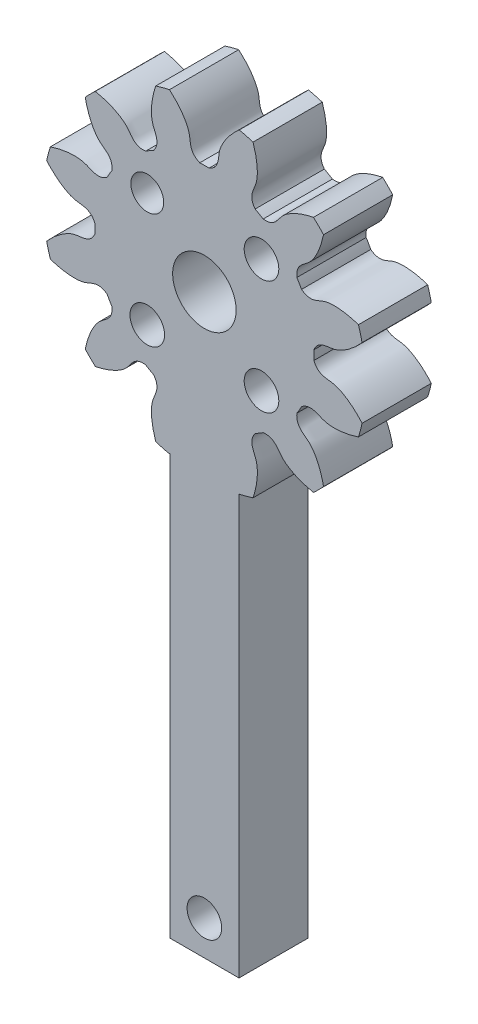
SolidWorks part; units mm, degrees
ref_plane "前视基准面" through (0, 0, 0) normal (0, 0, 1) x (1, 0, 0)
ref_plane "上视基准面" through (0, 0, 0) normal (0, 1, 0) x (1, 0, 0)
ref_plane "右视基准面" through (0, 0, 0) normal (1, 0, 0) x (0, 0, -1)
sketch "草图1" plane through (0, 0, 0) normal (0, 0, 1) x (1, 0, 0)
  circle A0 centre (0, 0) radius 14
extrude "凸台-拉伸1" add sketch "草图1" along normal blind 30
ref_axis "基准轴1" through (0, 0, 23.6995) along (0, 0, 1)
sketch "草图2" plane through (0, 0, 0) normal (0, 0, 1) x (1, 0, 0)
  line L0 (0, 0) -> (0, 14) construction
  circle A0 centre (0, 0) radius 14 construction
  arc A1 (0.4017, 9.4915) -> (-0.4017, 9.4915) centre (0, 0) ccw
  arc A2 (6.9952, 15.7899) -> (-6.9952, 15.7899) centre (0, 0) ccw
  spline S0 degree 3 poles (0.4017, 9.4915) (1.3616, 9.8986) (1.1487, 10.6896) (1.3523, 11.379) (1.3652, 11.4198) (1.3805, 11.4647) (1.3981, 11.5135) (1.4183, 11.5661) (1.4413, 11.6225) (1.4671, 11.6826) (1.4961, 11.7462) (1.5282, 11.8133) (1.5637, 11.8838) (1.6028, 11.9576) (1.6455, 12.0345) (1.6919, 12.1144) (1.7423, 12.1973) (1.7968, 12.2829) (1.8555, 12.3712) (1.9185, 12.462) (1.9859, 12.5552) (2.0579, 12.6506) (2.1346, 12.7481) (2.2161, 12.8475) (2.3025, 12.9487) (2.3939, 13.0516) (2.4904, 13.1559) (2.5921, 13.2615) (2.6991, 13.3682) (2.8114, 13.4759) (2.9292, 13.5844) (3.0525, 13.6935) (3.1814, 13.803) (3.316, 13.9128) (3.4563, 14.0226) (3.6023, 14.1323) (3.7542, 14.2418) (3.912, 14.3507) (4.0756, 14.4589) (4.2452, 14.5663) (4.4208, 14.6726) (4.6024, 14.7776) (4.79, 14.8811) (4.9836, 14.983) (5.1832, 15.083) (5.3889, 15.1809) (5.6006, 15.2765) (5.8183, 15.3697) (6.042, 15.4602) (6.2717, 15.5478) (6.5888, 15.6615) (6.8312, 15.7402) (6.9952, 15.7899) knots 0 0 0 0 0.218015 0.222044 0.226546 0.231522 0.236972 0.242897 0.249295 0.256167 0.263513 0.271332 0.279626 0.288394 0.297636 0.307351 0.317541 0.328204 0.339341 0.350953 0.363038 0.375597 0.38863 0.402137 0.416118 0.430573 0.445502 0.460904 0.476781 0.493132 0.509956 0.527255 0.545027 0.563273 0.581994 0.601188 0.620856 0.640998 0.661614 0.682704 0.704268 0.726305 0.748817 0.771803 0.795262 0.819196 0.843603 0.868484 0.89384 0.919669 0.945972 1 1 1 1
  spline S1 degree 3 poles (-0.4017, 9.4915) (-1.3616, 9.8986) (-1.1487, 10.6896) (-1.3523, 11.379) (-1.3652, 11.4198) (-1.3805, 11.4647) (-1.3981, 11.5135) (-1.4183, 11.5661) (-1.4413, 11.6225) (-1.4671, 11.6826) (-1.4961, 11.7462) (-1.5282, 11.8133) (-1.5637, 11.8838) (-1.6028, 11.9576) (-1.6455, 12.0345) (-1.6919, 12.1144) (-1.7423, 12.1973) (-1.7968, 12.2829) (-1.8555, 12.3712) (-1.9185, 12.462) (-1.9859, 12.5552) (-2.0579, 12.6506) (-2.1346, 12.7481) (-2.2161, 12.8475) (-2.3025, 12.9487) (-2.3939, 13.0516) (-2.4904, 13.1559) (-2.5921, 13.2615) (-2.6991, 13.3682) (-2.8114, 13.4759) (-2.9292, 13.5844) (-3.0525, 13.6935) (-3.1814, 13.803) (-3.316, 13.9128) (-3.4563, 14.0226) (-3.6023, 14.1323) (-3.7542, 14.2418) (-3.912, 14.3507) (-4.0756, 14.4589) (-4.2452, 14.5663) (-4.4208, 14.6726) (-4.6024, 14.7776) (-4.79, 14.8811) (-4.9836, 14.983) (-5.1832, 15.083) (-5.3889, 15.1809) (-5.6006, 15.2765) (-5.8183, 15.3697) (-6.042, 15.4602) (-6.2717, 15.5478) (-6.5888, 15.6615) (-6.8312, 15.7402) (-6.9952, 15.7899) knots 0 0 0 0 0.218015 0.222044 0.226546 0.231522 0.236972 0.242897 0.249295 0.256167 0.263513 0.271332 0.279626 0.288394 0.297636 0.307351 0.317541 0.328204 0.339341 0.350953 0.363038 0.375597 0.38863 0.402137 0.416118 0.430573 0.445502 0.460904 0.476781 0.493132 0.509956 0.527255 0.545027 0.563273 0.581994 0.601188 0.620856 0.640998 0.661614 0.682704 0.704268 0.726305 0.748817 0.771803 0.795262 0.819196 0.843603 0.868484 0.89384 0.919669 0.945972 1 1 1 1
extrude "切除-拉伸1" cut sketch "草图2" along normal through all
pattern_circular "阵列(圆周)1" count 12 every 30 about axis through (0, 0, 23.6995) along (0, 0, 1) of "切除-拉伸1"
sketch "草图3" plane through (0, 0, 0) normal (0, 0, 1) x (1, 0, 0)
  circle A0 centre (0, 0) radius 12 construction
  dimension "Dn" = 24
sketch "草图4" plane through (0, 0, 30) normal (0, 0, 1) x (1, 0, 0)
  line L0 (-4.75, 8.2272) -> (4.75, 8.2272) construction
  line L1 (4.95, -4.95) -> (-4.95, -4.95) construction
  line L2 (4.95, -4.95) -> (4.95, 4.95) construction
  line L3 (4.95, 4.95) -> (-4.95, 4.95) construction
  line L4 (-4.95, -4.95) -> (-4.95, 4.95) construction
  line L5 (4.95, -4.95) -> (-4.95, 4.95) construction
  line L6 (4.95, 4.95) -> (-4.95, -4.95) construction
  circle A0 centre (4.95, 4.95) radius 1.5
  circle A1 centre (4.95, -4.95) radius 1.5
  circle A2 centre (-4.95, -4.95) radius 1.5
  circle A3 centre (-4.95, 4.95) radius 1.4237
  arc A4 (-4.3979, 8.4207) -> (-5.0936, 8.019) centre (0, 0) ccw construction
  arc A5 (5.0936, 8.019) -> (4.3979, 8.4207) centre (0, 0) ccw construction
  point P0 (0, 0)
  dimension "D3" = 3
  dimension "D1" = 9.9
  dimension "D2" = 9.9
extrude "切除-拉伸2" cut sketch "草图4" against normal blind 10
sketch "草图5" plane through (0, 0, 0) normal (0, 0, -1) x (-1, 0, 0)
  arc A24 (5.0936, 8.019) -> (4.3979, 8.4207) centre (0, 0) ccw
  arc A25 (4.2145, 13.3506) -> (3.0255, 13.6692) centre (0, 0) ccw
  arc A26 (0.4017, 9.4915) -> (-0.4017, 9.4915) centre (0, 0) ccw
  arc A27 (-3.0255, 13.6692) -> (-4.2145, 13.3506) centre (0, 0) ccw
  arc A28 (-4.3979, 8.4207) -> (-5.0936, 8.019) centre (0, 0) ccw
  arc A29 (-9.4547, 10.3251) -> (-10.3251, 9.4547) centre (0, 0) ccw
  arc A30 (-8.019, 5.0936) -> (-8.4207, 4.3979) centre (0, 0) ccw
  arc A31 (-13.3506, 4.2145) -> (-13.6692, 3.0255) centre (0, 0) ccw
  arc A32 (-9.4915, 0.4017) -> (-9.4915, -0.4017) centre (0, 0) ccw
  arc A33 (-13.6692, -3.0255) -> (-13.3506, -4.2145) centre (0, 0) ccw
  arc A34 (-8.4207, -4.3979) -> (-8.019, -5.0936) centre (0, 0) ccw
  arc A35 (-10.3251, -9.4547) -> (-9.4547, -10.3251) centre (0, 0) ccw
  arc A36 (-5.0936, -8.019) -> (-4.3979, -8.4207) centre (0, 0) ccw
  arc A37 (-4.2145, -13.3506) -> (-3.0255, -13.6692) centre (0, 0) ccw
  arc A38 (-0.4017, -9.4915) -> (0.4017, -9.4915) centre (0, 0) ccw
  arc A39 (3.0255, -13.6692) -> (4.2145, -13.3506) centre (0, 0) ccw
  arc A40 (4.3979, -8.4207) -> (5.0936, -8.019) centre (0, 0) ccw
  arc A41 (9.4547, -10.3251) -> (10.3251, -9.4547) centre (0, 0) ccw
  arc A42 (8.019, -5.0936) -> (8.4207, -4.3979) centre (0, 0) ccw
  arc A43 (13.3506, -4.2145) -> (13.6692, -3.0255) centre (0, 0) ccw
  arc A44 (9.4915, -0.4017) -> (9.4915, 0.4017) centre (0, 0) ccw
  arc A45 (13.6692, 3.0255) -> (13.3506, 4.2145) centre (0, 0) ccw
  arc A46 (8.4207, 4.3979) -> (8.019, 5.0936) centre (0, 0) ccw
  arc A47 (10.3251, 9.4547) -> (9.4547, 10.3251) centre (0, 0) ccw
  arc A48 (5.0936, 8.019) -> (4.3979, 8.4207) centre (0, 0) ccw
  arc A49 (4.2145, 13.3506) -> (3.0255, 13.6692) centre (0, 0) ccw
  arc A50 (0.4017, 9.4915) -> (-0.4017, 9.4915) centre (0, 0) ccw
  arc A51 (-3.0255, 13.6692) -> (-4.2145, 13.3506) centre (0, 0) ccw
  arc A52 (-4.3979, 8.4207) -> (-5.0936, 8.019) centre (0, 0) ccw
  arc A53 (-9.4547, 10.3251) -> (-10.3251, 9.4547) centre (0, 0) ccw
  arc A54 (-8.019, 5.0936) -> (-8.4207, 4.3979) centre (0, 0) ccw
  arc A55 (-13.3506, 4.2145) -> (-13.6692, 3.0255) centre (0, 0) ccw
  arc A56 (-9.4915, 0.4017) -> (-9.4915, -0.4017) centre (0, 0) ccw
  arc A57 (-13.6692, -3.0255) -> (-13.3506, -4.2145) centre (0, 0) ccw
  arc A58 (-8.4207, -4.3979) -> (-8.019, -5.0936) centre (0, 0) ccw
  arc A59 (-10.3251, -9.4547) -> (-9.4547, -10.3251) centre (0, 0) ccw
  arc A60 (-5.0936, -8.019) -> (-4.3979, -8.4207) centre (0, 0) ccw
  arc A61 (-4.2145, -13.3506) -> (-3.0255, -13.6692) centre (0, 0) ccw
  arc A62 (-0.4017, -9.4915) -> (0.4017, -9.4915) centre (0, 0) ccw
  arc A63 (3.0255, -13.6692) -> (4.2145, -13.3506) centre (0, 0) ccw
  arc A64 (4.3979, -8.4207) -> (5.0936, -8.019) centre (0, 0) ccw
  arc A65 (9.4547, -10.3251) -> (10.3251, -9.4547) centre (0, 0) ccw
  arc A66 (8.019, -5.0936) -> (8.4207, -4.3979) centre (0, 0) ccw
  arc A67 (13.3506, -4.2145) -> (13.6692, -3.0255) centre (0, 0) ccw
  arc A68 (9.4915, -0.4017) -> (9.4915, 0.4017) centre (0, 0) ccw
  arc A69 (13.6692, 3.0255) -> (13.3506, 4.2145) centre (0, 0) ccw
  arc A70 (8.4207, 4.3979) -> (8.019, 5.0936) centre (0, 0) ccw
  arc A71 (10.3251, 9.4547) -> (9.4547, 10.3251) centre (0, 0) ccw
  spline S24 degree 3 poles (-2368.8794, 1837.9661) (113.0421, -150.6443) (38.3111, 18.3423) (8.7386, 10.1508) (8.4722, 10.0654) (8.2264, 9.9757) (8.0011, 9.883) (7.7961, 9.789) (7.6111, 9.695) (7.4457, 9.6025) (7.2995, 9.5129) (7.172, 9.4276) (7.0778, 9.359) (6.9977, 9.2968) (6.9309, 9.2418) (6.8721, 9.1892) (0.5786, 3.2069) (39.4786, -48.9386) (-2052.1534, 2191.1398) knots -9.086932 -9.086932 -9.086932 -9.086932 0.523219 0.554498 0.583882 0.61137 0.636962 0.660659 0.682459 0.702364 0.720374 0.736487 0.750705 0.757103 0.768478 0.777956 0.781985 3.505334 3.505334 3.505334 3.505334 only from (9.4547, 10.3251) to (5.0936, 8.019)
  spline S25 degree 3 poles (2923.6721, -681.6501) (-62.1215, 9.7202) (2.4879, 2.1045) (4.522, 10.546) (4.5381, 10.6233) (4.556, 10.7301) (4.5718, 10.8554) (4.5842, 10.9992) (4.5917, 11.1614) (4.5929, 11.3419) (4.5862, 11.5403) (4.5702, 11.7563) (4.5437, 11.9893) (4.505, 12.239) (4.453, 12.5046) (4.3862, 12.7855) (-4.0276, 42.7945) (-187.8553, 19.7333) (2778.1998, -1127.4538) knots -2.505338 -2.505338 -2.505338 -2.505338 0.218015 0.222044 0.231522 0.242897 0.256167 0.271332 0.288394 0.307351 0.328204 0.350953 0.375597 0.402137 0.430573 0.460904 0.493132 10.252695 10.252695 10.252695 10.252695 only from (4.3979, 8.4207) to (4.2145, 13.3506)
  spline S26 degree 3 poles (-2970.4928, 407.2856) (173.2195, -73.9407) (24.0073, 35.0405) (2.4924, 13.1601) (2.3045, 12.953) (2.1365, 12.7524) (1.9877, 12.5595) (1.8571, 12.3755) (1.7439, 12.2016) (1.6469, 12.0389) (1.5651, 11.8882) (1.4973, 11.7506) (1.4501, 11.6441) (1.4118, 11.5501) (1.3815, 11.4691) (1.3568, 11.3941) (-1.1024, 3.0665) (58.6587, -22.6428) (-2872.7869, 871.506) knots -9.086932 -9.086932 -9.086932 -9.086932 0.523219 0.554498 0.583882 0.61137 0.636962 0.660659 0.682459 0.702364 0.720374 0.736487 0.750705 0.757103 0.768478 0.777956 0.781985 3.505334 3.505334 3.505334 3.505334 only from (3.0255, 13.6692) to (0.4017, 9.4915)
  spline S27 degree 3 poles (2872.7993, 871.5098) (-58.6589, -22.6429) (1.1024, 3.0665) (-1.3568, 11.3941) (-1.3815, 11.4691) (-1.4194, 11.5705) (-1.4684, 11.687) (-1.5295, 11.8177) (-1.6042, 11.962) (-1.6934, 12.1188) (-1.7984, 12.2873) (-1.9202, 12.4663) (-2.0597, 12.6549) (-2.218, 12.8518) (-2.3959, 13.0558) (-2.5942, 13.2657) (-24.8852, 35.0474) (-172.5541, -76.8381) (2969.7185, 412.6963) knots -2.505338 -2.505338 -2.505338 -2.505338 0.218015 0.222044 0.231522 0.242897 0.256167 0.271332 0.288394 0.307351 0.328204 0.350953 0.375597 0.402137 0.430573 0.460904 0.493132 10.252695 10.252695 10.252695 10.252695 only from (-0.4017, 9.4915) to (-3.0255, 13.6692)
  spline S28 degree 3 poles (-2776.1651, -1132.5267) (186.9828, 22.5752) (3.2707, 42.3496) (-4.4215, 12.6432) (-4.4808, 12.3699) (-4.5259, 12.1121) (-4.5584, 11.8707) (-4.5794, 11.6461) (-4.5906, 11.4389) (-4.5932, 11.2494) (-4.5887, 11.078) (-4.5786, 10.925) (-4.5662, 10.8091) (-4.5524, 10.7085) (-4.5381, 10.6233) (-4.522, 10.546) (-2.4879, 2.1045) (62.1214, 9.7201) (-2923.6594, -681.6471) knots -9.086932 -9.086932 -9.086932 -9.086932 0.523219 0.554498 0.583882 0.61137 0.636962 0.660659 0.682459 0.702364 0.720374 0.736487 0.750705 0.757103 0.768478 0.777956 0.781985 3.505334 3.505334 3.505334 3.505334 only from (-4.2145, 13.3506) to (-4.3979, 8.4207)
  spline S29 degree 3 poles (2052.1623, 2191.1493) (-39.4787, -48.9387) (-0.5786, 3.2069) (-6.8721, 9.1892) (-6.9309, 9.2418) (-7.0145, 9.3106) (-7.1151, 9.387) (-7.2335, 9.4697) (-7.3702, 9.5573) (-7.5259, 9.6485) (-7.7011, 9.7419) (-7.8961, 9.8361) (-8.1112, 9.9296) (-8.3468, 10.021) (-8.6028, 10.1087) (-8.8795, 10.1914) (-39.0749, 17.9093) (-111.0172, -152.8208) (2365.5035, 1842.2647) knots -2.505338 -2.505338 -2.505338 -2.505338 0.218015 0.222044 0.231522 0.242897 0.256167 0.271332 0.288394 0.307351 0.328204 0.350953 0.375597 0.402137 0.430573 0.460904 0.493132 10.252695 10.252695 10.252695 10.252695 only from (-5.0936, 8.019) to (-9.4547, 10.3251)
  spline S30 degree 3 poles (-1837.9661, -2368.8794) (150.6443, 113.0421) (-18.3423, 38.3111) (-10.1508, 8.7386) (-10.0654, 8.4722) (-9.9757, 8.2264) (-9.883, 8.0011) (-9.789, 7.7961) (-9.695, 7.6111) (-9.6025, 7.4457) (-9.5129, 7.2995) (-9.4276, 7.172) (-9.359, 7.0778) (-9.2968, 6.9977) (-9.2418, 6.9309) (-9.1892, 6.8721) (-3.2069, 0.5786) (48.9386, 39.4786) (-2191.1398, -2052.1534) knots -9.086932 -9.086932 -9.086932 -9.086932 0.523219 0.554498 0.583882 0.61137 0.636962 0.660659 0.682459 0.702364 0.720374 0.736487 0.750705 0.757103 0.768478 0.777956 0.781985 3.505334 3.505334 3.505334 3.505334 only from (-10.3251, 9.4547) to (-8.019, 5.0936)
  spline S31 degree 3 poles (681.6501, 2923.6721) (-9.7202, -62.1215) (-2.1045, 2.4879) (-10.546, 4.522) (-10.6233, 4.5381) (-10.7301, 4.556) (-10.8554, 4.5718) (-10.9992, 4.5842) (-11.1614, 4.5917) (-11.3419, 4.5929) (-11.5403, 4.5862) (-11.7563, 4.5702) (-11.9893, 4.5437) (-12.239, 4.505) (-12.5046, 4.453) (-12.7855, 4.3862) (-42.7945, -4.0276) (-19.7333, -187.8553) (1127.4538, 2778.1998) knots -2.505338 -2.505338 -2.505338 -2.505338 0.218015 0.222044 0.231522 0.242897 0.256167 0.271332 0.288394 0.307351 0.328204 0.350953 0.375597 0.402137 0.430573 0.460904 0.493132 10.252695 10.252695 10.252695 10.252695 only from (-8.4207, 4.3979) to (-13.3506, 4.2145)
  spline S32 degree 3 poles (-407.2856, -2970.4928) (73.9407, 173.2195) (-35.0405, 24.0073) (-13.1601, 2.4924) (-12.953, 2.3045) (-12.7524, 2.1365) (-12.5595, 1.9877) (-12.3755, 1.8571) (-12.2016, 1.7439) (-12.0389, 1.6469) (-11.8882, 1.5651) (-11.7506, 1.4973) (-11.6441, 1.4501) (-11.5501, 1.4118) (-11.4691, 1.3815) (-11.3941, 1.3568) (-3.0665, -1.1024) (22.6428, 58.6587) (-871.506, -2872.7869) knots -9.086932 -9.086932 -9.086932 -9.086932 0.523219 0.554498 0.583882 0.61137 0.636962 0.660659 0.682459 0.702364 0.720374 0.736487 0.750705 0.757103 0.768478 0.777956 0.781985 3.505334 3.505334 3.505334 3.505334 only from (-13.6692, 3.0255) to (-9.4915, 0.4017)
  spline S33 degree 3 poles (-871.5098, 2872.7993) (22.6429, -58.6589) (-3.0665, 1.1024) (-11.3941, -1.3568) (-11.4691, -1.3815) (-11.5705, -1.4194) (-11.687, -1.4684) (-11.8177, -1.5295) (-11.962, -1.6042) (-12.1188, -1.6934) (-12.2873, -1.7984) (-12.4663, -1.9202) (-12.6549, -2.0597) (-12.8518, -2.218) (-13.0558, -2.3959) (-13.2657, -2.5942) (-35.0474, -24.8852) (76.8381, -172.5541) (-412.6963, 2969.7185) knots -2.505338 -2.505338 -2.505338 -2.505338 0.218015 0.222044 0.231522 0.242897 0.256167 0.271332 0.288394 0.307351 0.328204 0.350953 0.375597 0.402137 0.430573 0.460904 0.493132 10.252695 10.252695 10.252695 10.252695 only from (-9.4915, -0.4017) to (-13.6692, -3.0255)
  spline S34 degree 3 poles (1132.5267, -2776.1651) (-22.5752, 186.9828) (-42.3496, 3.2707) (-12.6432, -4.4215) (-12.3699, -4.4808) (-12.1121, -4.5259) (-11.8707, -4.5584) (-11.6461, -4.5794) (-11.4389, -4.5906) (-11.2494, -4.5932) (-11.078, -4.5887) (-10.925, -4.5786) (-10.8091, -4.5662) (-10.7085, -4.5524) (-10.6233, -4.5381) (-10.546, -4.522) (-2.1045, -2.4879) (-9.7201, 62.1214) (681.6471, -2923.6594) knots -9.086932 -9.086932 -9.086932 -9.086932 0.523219 0.554498 0.583882 0.61137 0.636962 0.660659 0.682459 0.702364 0.720374 0.736487 0.750705 0.757103 0.768478 0.777956 0.781985 3.505334 3.505334 3.505334 3.505334 only from (-13.3506, -4.2145) to (-8.4207, -4.3979)
  spline S35 degree 3 poles (-2191.1493, 2052.1623) (48.9387, -39.4787) (-3.2069, -0.5786) (-9.1892, -6.8721) (-9.2418, -6.9309) (-9.3106, -7.0145) (-9.387, -7.1151) (-9.4697, -7.2335) (-9.5573, -7.3702) (-9.6485, -7.5259) (-9.7419, -7.7011) (-9.8361, -7.8961) (-9.9296, -8.1112) (-10.021, -8.3468) (-10.1087, -8.6028) (-10.1914, -8.8795) (-17.9093, -39.0749) (152.8208, -111.0172) (-1842.2647, 2365.5035) knots -2.505338 -2.505338 -2.505338 -2.505338 0.218015 0.222044 0.231522 0.242897 0.256167 0.271332 0.288394 0.307351 0.328204 0.350953 0.375597 0.402137 0.430573 0.460904 0.493132 10.252695 10.252695 10.252695 10.252695 only from (-8.019, -5.0936) to (-10.3251, -9.4547)
  spline S36 degree 3 poles (2368.8794, -1837.9661) (-113.0421, 150.6443) (-38.3111, -18.3423) (-8.7386, -10.1508) (-8.4722, -10.0654) (-8.2264, -9.9757) (-8.0011, -9.883) (-7.7961, -9.789) (-7.6111, -9.695) (-7.4457, -9.6025) (-7.2995, -9.5129) (-7.172, -9.4276) (-7.0778, -9.359) (-6.9977, -9.2968) (-6.9309, -9.2418) (-6.8721, -9.1892) (-0.5786, -3.2069) (-39.4786, 48.9386) (2052.1534, -2191.1398) knots -9.086932 -9.086932 -9.086932 -9.086932 0.523219 0.554498 0.583882 0.61137 0.636962 0.660659 0.682459 0.702364 0.720374 0.736487 0.750705 0.757103 0.768478 0.777956 0.781985 3.505334 3.505334 3.505334 3.505334 only from (-9.4547, -10.3251) to (-5.0936, -8.019)
  spline S37 degree 3 poles (-2923.6721, 681.6501) (62.1215, -9.7202) (-2.4879, -2.1045) (-4.522, -10.546) (-4.5381, -10.6233) (-4.556, -10.7301) (-4.5718, -10.8554) (-4.5842, -10.9992) (-4.5917, -11.1614) (-4.5929, -11.3419) (-4.5862, -11.5403) (-4.5702, -11.7563) (-4.5437, -11.9893) (-4.505, -12.239) (-4.453, -12.5046) (-4.3862, -12.7855) (4.0276, -42.7945) (187.8553, -19.7333) (-2778.1998, 1127.4538) knots -2.505338 -2.505338 -2.505338 -2.505338 0.218015 0.222044 0.231522 0.242897 0.256167 0.271332 0.288394 0.307351 0.328204 0.350953 0.375597 0.402137 0.430573 0.460904 0.493132 10.252695 10.252695 10.252695 10.252695 only from (-4.3979, -8.4207) to (-4.2145, -13.3506)
  spline S38 degree 3 poles (2970.4928, -407.2856) (-173.2195, 73.9407) (-24.0073, -35.0405) (-2.4924, -13.1601) (-2.3045, -12.953) (-2.1365, -12.7524) (-1.9877, -12.5595) (-1.8571, -12.3755) (-1.7439, -12.2016) (-1.6469, -12.0389) (-1.5651, -11.8882) (-1.4973, -11.7506) (-1.4501, -11.6441) (-1.4118, -11.5501) (-1.3815, -11.4691) (-1.3568, -11.3941) (1.1024, -3.0665) (-58.6587, 22.6428) (2872.7869, -871.506) knots -9.086932 -9.086932 -9.086932 -9.086932 0.523219 0.554498 0.583882 0.61137 0.636962 0.660659 0.682459 0.702364 0.720374 0.736487 0.750705 0.757103 0.768478 0.777956 0.781985 3.505334 3.505334 3.505334 3.505334 only from (-3.0255, -13.6692) to (-0.4017, -9.4915)
  spline S39 degree 3 poles (-2872.7993, -871.5098) (58.6589, 22.6429) (-1.1024, -3.0665) (1.3568, -11.3941) (1.3815, -11.4691) (1.4194, -11.5705) (1.4684, -11.687) (1.5295, -11.8177) (1.6042, -11.962) (1.6934, -12.1188) (1.7984, -12.2873) (1.9202, -12.4663) (2.0597, -12.6549) (2.218, -12.8518) (2.3959, -13.0558) (2.5942, -13.2657) (24.8852, -35.0474) (172.5541, 76.8381) (-2969.7185, -412.6963) knots -2.505338 -2.505338 -2.505338 -2.505338 0.218015 0.222044 0.231522 0.242897 0.256167 0.271332 0.288394 0.307351 0.328204 0.350953 0.375597 0.402137 0.430573 0.460904 0.493132 10.252695 10.252695 10.252695 10.252695 only from (0.4017, -9.4915) to (3.0255, -13.6692)
  spline S40 degree 3 poles (2776.1651, 1132.5267) (-186.9828, -22.5752) (-3.2707, -42.3496) (4.4215, -12.6432) (4.4808, -12.3699) (4.5259, -12.1121) (4.5584, -11.8707) (4.5794, -11.6461) (4.5906, -11.4389) (4.5932, -11.2494) (4.5887, -11.078) (4.5786, -10.925) (4.5662, -10.8091) (4.5524, -10.7085) (4.5381, -10.6233) (4.522, -10.546) (2.4879, -2.1045) (-62.1214, -9.7201) (2923.6594, 681.6471) knots -9.086932 -9.086932 -9.086932 -9.086932 0.523219 0.554498 0.583882 0.61137 0.636962 0.660659 0.682459 0.702364 0.720374 0.736487 0.750705 0.757103 0.768478 0.777956 0.781985 3.505334 3.505334 3.505334 3.505334 only from (4.2145, -13.3506) to (4.3979, -8.4207)
  spline S41 degree 3 poles (-2052.1623, -2191.1493) (39.4787, 48.9387) (0.5786, -3.2069) (6.8721, -9.1892) (6.9309, -9.2418) (7.0145, -9.3106) (7.1151, -9.387) (7.2335, -9.4697) (7.3702, -9.5573) (7.5259, -9.6485) (7.7011, -9.7419) (7.8961, -9.8361) (8.1112, -9.9296) (8.3468, -10.021) (8.6028, -10.1087) (8.8795, -10.1914) (39.0749, -17.9093) (111.0172, 152.8208) (-2365.5035, -1842.2647) knots -2.505338 -2.505338 -2.505338 -2.505338 0.218015 0.222044 0.231522 0.242897 0.256167 0.271332 0.288394 0.307351 0.328204 0.350953 0.375597 0.402137 0.430573 0.460904 0.493132 10.252695 10.252695 10.252695 10.252695 only from (5.0936, -8.019) to (9.4547, -10.3251)
  spline S42 degree 3 poles (1837.9661, 2368.8794) (-150.6443, -113.0421) (18.3423, -38.3111) (10.1508, -8.7386) (10.0654, -8.4722) (9.9757, -8.2264) (9.883, -8.0011) (9.789, -7.7961) (9.695, -7.6111) (9.6025, -7.4457) (9.5129, -7.2995) (9.4276, -7.172) (9.359, -7.0778) (9.2968, -6.9977) (9.2418, -6.9309) (9.1892, -6.8721) (3.2069, -0.5786) (-48.9386, -39.4786) (2191.1398, 2052.1534) knots -9.086932 -9.086932 -9.086932 -9.086932 0.523219 0.554498 0.583882 0.61137 0.636962 0.660659 0.682459 0.702364 0.720374 0.736487 0.750705 0.757103 0.768478 0.777956 0.781985 3.505334 3.505334 3.505334 3.505334 only from (10.3251, -9.4547) to (8.019, -5.0936)
  spline S43 degree 3 poles (-681.6501, -2923.6721) (9.7202, 62.1215) (2.1045, -2.4879) (10.546, -4.522) (10.6233, -4.5381) (10.7301, -4.556) (10.8554, -4.5718) (10.9992, -4.5842) (11.1614, -4.5917) (11.3419, -4.5929) (11.5403, -4.5862) (11.7563, -4.5702) (11.9893, -4.5437) (12.239, -4.505) (12.5046, -4.453) (12.7855, -4.3862) (42.7945, 4.0276) (19.7333, 187.8553) (-1127.4538, -2778.1998) knots -2.505338 -2.505338 -2.505338 -2.505338 0.218015 0.222044 0.231522 0.242897 0.256167 0.271332 0.288394 0.307351 0.328204 0.350953 0.375597 0.402137 0.430573 0.460904 0.493132 10.252695 10.252695 10.252695 10.252695 only from (8.4207, -4.3979) to (13.3506, -4.2145)
  spline S44 degree 3 poles (407.2856, 2970.4928) (-73.9407, -173.2195) (35.0405, -24.0073) (13.1601, -2.4924) (12.953, -2.3045) (12.7524, -2.1365) (12.5595, -1.9877) (12.3755, -1.8571) (12.2016, -1.7439) (12.0389, -1.6469) (11.8882, -1.5651) (11.7506, -1.4973) (11.6441, -1.4501) (11.5501, -1.4118) (11.4691, -1.3815) (11.3941, -1.3568) (3.0665, 1.1024) (-22.6428, -58.6587) (871.506, 2872.7869) knots -9.086932 -9.086932 -9.086932 -9.086932 0.523219 0.554498 0.583882 0.61137 0.636962 0.660659 0.682459 0.702364 0.720374 0.736487 0.750705 0.757103 0.768478 0.777956 0.781985 3.505334 3.505334 3.505334 3.505334 only from (13.6692, -3.0255) to (9.4915, -0.4017)
  spline S45 degree 3 poles (871.5098, -2872.7993) (-22.6429, 58.6589) (3.0665, -1.1024) (11.3941, 1.3568) (11.4691, 1.3815) (11.5705, 1.4194) (11.687, 1.4684) (11.8177, 1.5295) (11.962, 1.6042) (12.1188, 1.6934) (12.2873, 1.7984) (12.4663, 1.9202) (12.6549, 2.0597) (12.8518, 2.218) (13.0558, 2.3959) (13.2657, 2.5942) (35.0474, 24.8852) (-76.8381, 172.5541) (412.6963, -2969.7185) knots -2.505338 -2.505338 -2.505338 -2.505338 0.218015 0.222044 0.231522 0.242897 0.256167 0.271332 0.288394 0.307351 0.328204 0.350953 0.375597 0.402137 0.430573 0.460904 0.493132 10.252695 10.252695 10.252695 10.252695 only from (9.4915, 0.4017) to (13.6692, 3.0255)
  spline S46 degree 3 poles (-1132.5267, 2776.1651) (22.5752, -186.9828) (42.3496, -3.2707) (12.6432, 4.4215) (12.3699, 4.4808) (12.1121, 4.5259) (11.8707, 4.5584) (11.6461, 4.5794) (11.4389, 4.5906) (11.2494, 4.5932) (11.078, 4.5887) (10.925, 4.5786) (10.8091, 4.5662) (10.7085, 4.5524) (10.6233, 4.5381) (10.546, 4.522) (2.1045, 2.4879) (9.7201, -62.1214) (-681.6471, 2923.6594) knots -9.086932 -9.086932 -9.086932 -9.086932 0.523219 0.554498 0.583882 0.61137 0.636962 0.660659 0.682459 0.702364 0.720374 0.736487 0.750705 0.757103 0.768478 0.777956 0.781985 3.505334 3.505334 3.505334 3.505334 only from (13.3506, 4.2145) to (8.4207, 4.3979)
  spline S47 degree 3 poles (2191.1493, -2052.1623) (-48.9387, 39.4787) (3.2069, 0.5786) (9.1892, 6.8721) (9.2418, 6.9309) (9.3106, 7.0145) (9.387, 7.1151) (9.4697, 7.2335) (9.5573, 7.3702) (9.6485, 7.5259) (9.7419, 7.7011) (9.8361, 7.8961) (9.9296, 8.1112) (10.021, 8.3468) (10.1087, 8.6028) (10.1914, 8.8795) (17.9093, 39.0749) (-152.8208, 111.0172) (1842.2647, -2365.5035) knots -2.505338 -2.505338 -2.505338 -2.505338 0.218015 0.222044 0.231522 0.242897 0.256167 0.271332 0.288394 0.307351 0.328204 0.350953 0.375597 0.402137 0.430573 0.460904 0.493132 10.252695 10.252695 10.252695 10.252695 only from (8.019, 5.0936) to (10.3251, 9.4547)
  spline S48 degree 3 poles (9.4547, 10.3251) (9.309, 10.2963) (9.0672, 10.2418) (8.7386, 10.1508) (8.4722, 10.0654) (8.2264, 9.9757) (8.0011, 9.883) (7.7961, 9.789) (7.6111, 9.695) (7.4457, 9.6025) (7.2995, 9.5129) (7.172, 9.4276) (7.0778, 9.359) (6.9977, 9.2968) (6.9309, 9.2418) (6.8721, 9.1892) (6.3397, 8.6831) (6.1285, 7.8917) (5.0936, 8.019) knots 0.476404 0.476404 0.476404 0.476404 0.523219 0.554498 0.583882 0.61137 0.636962 0.660659 0.682459 0.702364 0.720374 0.736487 0.750705 0.757103 0.768478 0.777956 0.781985 1 1 1 1
  spline S49 degree 3 poles (4.3979, 8.4207) (3.7701, 9.2532) (4.35, 9.8319) (4.522, 10.546) (4.5381, 10.6233) (4.556, 10.7301) (4.5718, 10.8554) (4.5842, 10.9992) (4.5917, 11.1614) (4.5929, 11.3419) (4.5862, 11.5403) (4.5702, 11.7563) (4.5437, 11.9893) (4.505, 12.239) (4.453, 12.5046) (4.3862, 12.7855) (4.3065, 13.0698) (4.2457, 13.2591) (4.2145, 13.3506) knots 0 0 0 0 0.218015 0.222044 0.231522 0.242897 0.256167 0.271332 0.288394 0.307351 0.328204 0.350953 0.375597 0.402137 0.430573 0.460904 0.493132 0.523596 0.523596 0.523596 0.523596
  spline S50 degree 3 poles (3.0255, 13.6692) (2.9137, 13.5714) (2.7316, 13.4033) (2.4924, 13.1601) (2.3045, 12.953) (2.1365, 12.7524) (1.9877, 12.5595) (1.8571, 12.3755) (1.7439, 12.2016) (1.6469, 12.0389) (1.5651, 11.8882) (1.4973, 11.7506) (1.4501, 11.6441) (1.4118, 11.5501) (1.3815, 11.4691) (1.3568, 11.3941) (1.1487, 10.6896) (1.3616, 9.8986) (0.4017, 9.4915) knots 0.476404 0.476404 0.476404 0.476404 0.523219 0.554498 0.583882 0.61137 0.636962 0.660659 0.682459 0.702364 0.720374 0.736487 0.750705 0.757103 0.768478 0.777956 0.781985 1 1 1 1
  spline S51 degree 3 poles (-0.4017, 9.4915) (-1.3616, 9.8986) (-1.1487, 10.6896) (-1.3568, 11.3941) (-1.3815, 11.4691) (-1.4194, 11.5705) (-1.4684, 11.687) (-1.5295, 11.8177) (-1.6042, 11.962) (-1.6934, 12.1188) (-1.7984, 12.2873) (-1.9202, 12.4663) (-2.0597, 12.6549) (-2.218, 12.8518) (-2.3959, 13.0558) (-2.5942, 13.2657) (-2.8053, 13.472) (-2.9527, 13.6056) (-3.0255, 13.6692) knots 0 0 0 0 0.218015 0.222044 0.231522 0.242897 0.256167 0.271332 0.288394 0.307351 0.328204 0.350953 0.375597 0.402137 0.430573 0.460904 0.493132 0.523596 0.523596 0.523596 0.523596
  spline S52 degree 3 poles (-4.2145, 13.3506) (-4.2624, 13.21) (-4.3361, 12.9734) (-4.4215, 12.6432) (-4.4808, 12.3699) (-4.5259, 12.1121) (-4.5584, 11.8707) (-4.5794, 11.6461) (-4.5906, 11.4389) (-4.5932, 11.2494) (-4.5887, 11.078) (-4.5786, 10.925) (-4.5662, 10.8091) (-4.5524, 10.7085) (-4.5381, 10.6233) (-4.522, 10.546) (-4.35, 9.8319) (-3.7701, 9.2532) (-4.3979, 8.4207) knots 0.476404 0.476404 0.476404 0.476404 0.523219 0.554498 0.583882 0.61137 0.636962 0.660659 0.682459 0.702364 0.720374 0.736487 0.750705 0.757103 0.768478 0.777956 0.781985 1 1 1 1
  spline S53 degree 3 poles (-5.0936, 8.019) (-6.1285, 7.8917) (-6.3397, 8.6831) (-6.8721, 9.1892) (-6.9309, 9.2418) (-7.0145, 9.3106) (-7.1151, 9.387) (-7.2335, 9.4697) (-7.3702, 9.5573) (-7.5259, 9.6485) (-7.7011, 9.7419) (-7.8961, 9.8361) (-8.1112, 9.9296) (-8.3468, 10.021) (-8.6028, 10.1087) (-8.8795, 10.1914) (-9.1655, 10.2645) (-9.3599, 10.3064) (-9.4547, 10.3251) knots 0 0 0 0 0.218015 0.222044 0.231522 0.242897 0.256167 0.271332 0.288394 0.307351 0.328204 0.350953 0.375597 0.402137 0.430573 0.460904 0.493132 0.523596 0.523596 0.523596 0.523596
  spline S54 degree 3 poles (-10.3251, 9.4547) (-10.2963, 9.309) (-10.2418, 9.0672) (-10.1508, 8.7386) (-10.0654, 8.4722) (-9.9757, 8.2264) (-9.883, 8.0011) (-9.789, 7.7961) (-9.695, 7.6111) (-9.6025, 7.4457) (-9.5129, 7.2995) (-9.4276, 7.172) (-9.359, 7.0778) (-9.2968, 6.9977) (-9.2418, 6.9309) (-9.1892, 6.8721) (-8.6831, 6.3397) (-7.8917, 6.1285) (-8.019, 5.0936) knots 0.476404 0.476404 0.476404 0.476404 0.523219 0.554498 0.583882 0.61137 0.636962 0.660659 0.682459 0.702364 0.720374 0.736487 0.750705 0.757103 0.768478 0.777956 0.781985 1 1 1 1
  spline S55 degree 3 poles (-8.4207, 4.3979) (-9.2532, 3.7701) (-9.8319, 4.35) (-10.546, 4.522) (-10.6233, 4.5381) (-10.7301, 4.556) (-10.8554, 4.5718) (-10.9992, 4.5842) (-11.1614, 4.5917) (-11.3419, 4.5929) (-11.5403, 4.5862) (-11.7563, 4.5702) (-11.9893, 4.5437) (-12.239, 4.505) (-12.5046, 4.453) (-12.7855, 4.3862) (-13.0698, 4.3065) (-13.2591, 4.2457) (-13.3506, 4.2145) knots 0 0 0 0 0.218015 0.222044 0.231522 0.242897 0.256167 0.271332 0.288394 0.307351 0.328204 0.350953 0.375597 0.402137 0.430573 0.460904 0.493132 0.523596 0.523596 0.523596 0.523596
  spline S56 degree 3 poles (-13.6692, 3.0255) (-13.5714, 2.9137) (-13.4033, 2.7316) (-13.1601, 2.4924) (-12.953, 2.3045) (-12.7524, 2.1365) (-12.5595, 1.9877) (-12.3755, 1.8571) (-12.2016, 1.7439) (-12.0389, 1.6469) (-11.8882, 1.5651) (-11.7506, 1.4973) (-11.6441, 1.4501) (-11.5501, 1.4118) (-11.4691, 1.3815) (-11.3941, 1.3568) (-10.6896, 1.1487) (-9.8986, 1.3616) (-9.4915, 0.4017) knots 0.476404 0.476404 0.476404 0.476404 0.523219 0.554498 0.583882 0.61137 0.636962 0.660659 0.682459 0.702364 0.720374 0.736487 0.750705 0.757103 0.768478 0.777956 0.781985 1 1 1 1
  spline S57 degree 3 poles (-9.4915, -0.4017) (-9.8986, -1.3616) (-10.6896, -1.1487) (-11.3941, -1.3568) (-11.4691, -1.3815) (-11.5705, -1.4194) (-11.687, -1.4684) (-11.8177, -1.5295) (-11.962, -1.6042) (-12.1188, -1.6934) (-12.2873, -1.7984) (-12.4663, -1.9202) (-12.6549, -2.0597) (-12.8518, -2.218) (-13.0558, -2.3959) (-13.2657, -2.5942) (-13.472, -2.8053) (-13.6056, -2.9527) (-13.6692, -3.0255) knots 0 0 0 0 0.218015 0.222044 0.231522 0.242897 0.256167 0.271332 0.288394 0.307351 0.328204 0.350953 0.375597 0.402137 0.430573 0.460904 0.493132 0.523596 0.523596 0.523596 0.523596
  spline S58 degree 3 poles (-13.3506, -4.2145) (-13.21, -4.2624) (-12.9734, -4.3361) (-12.6432, -4.4215) (-12.3699, -4.4808) (-12.1121, -4.5259) (-11.8707, -4.5584) (-11.6461, -4.5794) (-11.4389, -4.5906) (-11.2494, -4.5932) (-11.078, -4.5887) (-10.925, -4.5786) (-10.8091, -4.5662) (-10.7085, -4.5524) (-10.6233, -4.5381) (-10.546, -4.522) (-9.8319, -4.35) (-9.2532, -3.7701) (-8.4207, -4.3979) knots 0.476404 0.476404 0.476404 0.476404 0.523219 0.554498 0.583882 0.61137 0.636962 0.660659 0.682459 0.702364 0.720374 0.736487 0.750705 0.757103 0.768478 0.777956 0.781985 1 1 1 1
  spline S59 degree 3 poles (-8.019, -5.0936) (-7.8917, -6.1285) (-8.6831, -6.3397) (-9.1892, -6.8721) (-9.2418, -6.9309) (-9.3106, -7.0145) (-9.387, -7.1151) (-9.4697, -7.2335) (-9.5573, -7.3702) (-9.6485, -7.5259) (-9.7419, -7.7011) (-9.8361, -7.8961) (-9.9296, -8.1112) (-10.021, -8.3468) (-10.1087, -8.6028) (-10.1914, -8.8795) (-10.2645, -9.1655) (-10.3064, -9.3599) (-10.3251, -9.4547) knots 0 0 0 0 0.218015 0.222044 0.231522 0.242897 0.256167 0.271332 0.288394 0.307351 0.328204 0.350953 0.375597 0.402137 0.430573 0.460904 0.493132 0.523596 0.523596 0.523596 0.523596
  spline S60 degree 3 poles (-9.4547, -10.3251) (-9.309, -10.2963) (-9.0672, -10.2418) (-8.7386, -10.1508) (-8.4722, -10.0654) (-8.2264, -9.9757) (-8.0011, -9.883) (-7.7961, -9.789) (-7.6111, -9.695) (-7.4457, -9.6025) (-7.2995, -9.5129) (-7.172, -9.4276) (-7.0778, -9.359) (-6.9977, -9.2968) (-6.9309, -9.2418) (-6.8721, -9.1892) (-6.3397, -8.6831) (-6.1285, -7.8917) (-5.0936, -8.019) knots 0.476404 0.476404 0.476404 0.476404 0.523219 0.554498 0.583882 0.61137 0.636962 0.660659 0.682459 0.702364 0.720374 0.736487 0.750705 0.757103 0.768478 0.777956 0.781985 1 1 1 1
  spline S61 degree 3 poles (-4.3979, -8.4207) (-3.7701, -9.2532) (-4.35, -9.8319) (-4.522, -10.546) (-4.5381, -10.6233) (-4.556, -10.7301) (-4.5718, -10.8554) (-4.5842, -10.9992) (-4.5917, -11.1614) (-4.5929, -11.3419) (-4.5862, -11.5403) (-4.5702, -11.7563) (-4.5437, -11.9893) (-4.505, -12.239) (-4.453, -12.5046) (-4.3862, -12.7855) (-4.3065, -13.0698) (-4.2457, -13.2591) (-4.2145, -13.3506) knots 0 0 0 0 0.218015 0.222044 0.231522 0.242897 0.256167 0.271332 0.288394 0.307351 0.328204 0.350953 0.375597 0.402137 0.430573 0.460904 0.493132 0.523596 0.523596 0.523596 0.523596
  spline S62 degree 3 poles (-3.0255, -13.6692) (-2.9137, -13.5714) (-2.7316, -13.4033) (-2.4924, -13.1601) (-2.3045, -12.953) (-2.1365, -12.7524) (-1.9877, -12.5595) (-1.8571, -12.3755) (-1.7439, -12.2016) (-1.6469, -12.0389) (-1.5651, -11.8882) (-1.4973, -11.7506) (-1.4501, -11.6441) (-1.4118, -11.5501) (-1.3815, -11.4691) (-1.3568, -11.3941) (-1.1487, -10.6896) (-1.3616, -9.8986) (-0.4017, -9.4915) knots 0.476404 0.476404 0.476404 0.476404 0.523219 0.554498 0.583882 0.61137 0.636962 0.660659 0.682459 0.702364 0.720374 0.736487 0.750705 0.757103 0.768478 0.777956 0.781985 1 1 1 1
  spline S63 degree 3 poles (0.4017, -9.4915) (1.3616, -9.8986) (1.1487, -10.6896) (1.3568, -11.3941) (1.3815, -11.4691) (1.4194, -11.5705) (1.4684, -11.687) (1.5295, -11.8177) (1.6042, -11.962) (1.6934, -12.1188) (1.7984, -12.2873) (1.9202, -12.4663) (2.0597, -12.6549) (2.218, -12.8518) (2.3959, -13.0558) (2.5942, -13.2657) (2.8053, -13.472) (2.9527, -13.6056) (3.0255, -13.6692) knots 0 0 0 0 0.218015 0.222044 0.231522 0.242897 0.256167 0.271332 0.288394 0.307351 0.328204 0.350953 0.375597 0.402137 0.430573 0.460904 0.493132 0.523596 0.523596 0.523596 0.523596
  spline S64 degree 3 poles (4.2145, -13.3506) (4.2624, -13.21) (4.3361, -12.9734) (4.4215, -12.6432) (4.4808, -12.3699) (4.5259, -12.1121) (4.5584, -11.8707) (4.5794, -11.6461) (4.5906, -11.4389) (4.5932, -11.2494) (4.5887, -11.078) (4.5786, -10.925) (4.5662, -10.8091) (4.5524, -10.7085) (4.5381, -10.6233) (4.522, -10.546) (4.35, -9.8319) (3.7701, -9.2532) (4.3979, -8.4207) knots 0.476404 0.476404 0.476404 0.476404 0.523219 0.554498 0.583882 0.61137 0.636962 0.660659 0.682459 0.702364 0.720374 0.736487 0.750705 0.757103 0.768478 0.777956 0.781985 1 1 1 1
  spline S65 degree 3 poles (5.0936, -8.019) (6.1285, -7.8917) (6.3397, -8.6831) (6.8721, -9.1892) (6.9309, -9.2418) (7.0145, -9.3106) (7.1151, -9.387) (7.2335, -9.4697) (7.3702, -9.5573) (7.5259, -9.6485) (7.7011, -9.7419) (7.8961, -9.8361) (8.1112, -9.9296) (8.3468, -10.021) (8.6028, -10.1087) (8.8795, -10.1914) (9.1655, -10.2645) (9.3599, -10.3064) (9.4547, -10.3251) knots 0 0 0 0 0.218015 0.222044 0.231522 0.242897 0.256167 0.271332 0.288394 0.307351 0.328204 0.350953 0.375597 0.402137 0.430573 0.460904 0.493132 0.523596 0.523596 0.523596 0.523596
  spline S66 degree 3 poles (10.3251, -9.4547) (10.2963, -9.309) (10.2418, -9.0672) (10.1508, -8.7386) (10.0654, -8.4722) (9.9757, -8.2264) (9.883, -8.0011) (9.789, -7.7961) (9.695, -7.6111) (9.6025, -7.4457) (9.5129, -7.2995) (9.4276, -7.172) (9.359, -7.0778) (9.2968, -6.9977) (9.2418, -6.9309) (9.1892, -6.8721) (8.6831, -6.3397) (7.8917, -6.1285) (8.019, -5.0936) knots 0.476404 0.476404 0.476404 0.476404 0.523219 0.554498 0.583882 0.61137 0.636962 0.660659 0.682459 0.702364 0.720374 0.736487 0.750705 0.757103 0.768478 0.777956 0.781985 1 1 1 1
  spline S67 degree 3 poles (8.4207, -4.3979) (9.2532, -3.7701) (9.8319, -4.35) (10.546, -4.522) (10.6233, -4.5381) (10.7301, -4.556) (10.8554, -4.5718) (10.9992, -4.5842) (11.1614, -4.5917) (11.3419, -4.5929) (11.5403, -4.5862) (11.7563, -4.5702) (11.9893, -4.5437) (12.239, -4.505) (12.5046, -4.453) (12.7855, -4.3862) (13.0698, -4.3065) (13.2591, -4.2457) (13.3506, -4.2145) knots 0 0 0 0 0.218015 0.222044 0.231522 0.242897 0.256167 0.271332 0.288394 0.307351 0.328204 0.350953 0.375597 0.402137 0.430573 0.460904 0.493132 0.523596 0.523596 0.523596 0.523596
  spline S68 degree 3 poles (13.6692, -3.0255) (13.5714, -2.9137) (13.4033, -2.7316) (13.1601, -2.4924) (12.953, -2.3045) (12.7524, -2.1365) (12.5595, -1.9877) (12.3755, -1.8571) (12.2016, -1.7439) (12.0389, -1.6469) (11.8882, -1.5651) (11.7506, -1.4973) (11.6441, -1.4501) (11.5501, -1.4118) (11.4691, -1.3815) (11.3941, -1.3568) (10.6896, -1.1487) (9.8986, -1.3616) (9.4915, -0.4017) knots 0.476404 0.476404 0.476404 0.476404 0.523219 0.554498 0.583882 0.61137 0.636962 0.660659 0.682459 0.702364 0.720374 0.736487 0.750705 0.757103 0.768478 0.777956 0.781985 1 1 1 1
  spline S69 degree 3 poles (9.4915, 0.4017) (9.8986, 1.3616) (10.6896, 1.1487) (11.3941, 1.3568) (11.4691, 1.3815) (11.5705, 1.4194) (11.687, 1.4684) (11.8177, 1.5295) (11.962, 1.6042) (12.1188, 1.6934) (12.2873, 1.7984) (12.4663, 1.9202) (12.6549, 2.0597) (12.8518, 2.218) (13.0558, 2.3959) (13.2657, 2.5942) (13.472, 2.8053) (13.6056, 2.9527) (13.6692, 3.0255) knots 0 0 0 0 0.218015 0.222044 0.231522 0.242897 0.256167 0.271332 0.288394 0.307351 0.328204 0.350953 0.375597 0.402137 0.430573 0.460904 0.493132 0.523596 0.523596 0.523596 0.523596
  spline S70 degree 3 poles (13.3506, 4.2145) (13.21, 4.2624) (12.9734, 4.3361) (12.6432, 4.4215) (12.3699, 4.4808) (12.1121, 4.5259) (11.8707, 4.5584) (11.6461, 4.5794) (11.4389, 4.5906) (11.2494, 4.5932) (11.078, 4.5887) (10.925, 4.5786) (10.8091, 4.5662) (10.7085, 4.5524) (10.6233, 4.5381) (10.546, 4.522) (9.8319, 4.35) (9.2532, 3.7701) (8.4207, 4.3979) knots 0.476404 0.476404 0.476404 0.476404 0.523219 0.554498 0.583882 0.61137 0.636962 0.660659 0.682459 0.702364 0.720374 0.736487 0.750705 0.757103 0.768478 0.777956 0.781985 1 1 1 1
  spline S71 degree 3 poles (8.019, 5.0936) (7.8917, 6.1285) (8.6831, 6.3397) (9.1892, 6.8721) (9.2418, 6.9309) (9.3106, 7.0145) (9.387, 7.1151) (9.4697, 7.2335) (9.5573, 7.3702) (9.6485, 7.5259) (9.7419, 7.7011) (9.8361, 7.8961) (9.9296, 8.1112) (10.021, 8.3468) (10.1087, 8.6028) (10.1914, 8.8795) (10.2645, 9.1655) (10.3064, 9.3599) (10.3251, 9.4547) knots 0 0 0 0 0.218015 0.222044 0.231522 0.242897 0.256167 0.271332 0.288394 0.307351 0.328204 0.350953 0.375597 0.402137 0.430573 0.460904 0.493132 0.523596 0.523596 0.523596 0.523596
  dimension "D1" = 0
extrude "切除-拉伸3" cut sketch "草图5" against normal blind 24
sketch "草图6" plane through (0, 0, 30) normal (0, 0, 1) x (1, 0, 0)
  circle A0 centre (0, 0) radius 2.75
  dimension "D1" = 5.5
extrude "切除-拉伸4" cut sketch "草图6" against normal blind 24
sketch "草图9" plane through (0, 0, 30) normal (0, 0, 1) x (1, 0, 0)
  line L0 (0, 9.5) -> (0, -9.5) construction
  line L1 (3, -5) -> (-3, -5)
  line L2 (-3, -5) -> (-3, -50)
  line L3 (-3, -50) -> (3, -50)
  line L4 (3, -5) -> (3, -50)
  arc A0 (0.4017, 9.4915) -> (-0.4017, 9.4915) centre (0, 0) ccw construction
  arc A1 (-0.4017, -9.4915) -> (0.4017, -9.4915) centre (0, 0) ccw construction
  point P8 (0, 0)
  point P13 (0, -50)
  point P14 (0, -5)
  dimension "D1" = 3
  dimension "D2" = 45
  dimension "D3" = 5
extrude "凸台-拉伸2" add sketch "草图9" against normal blind 6
sketch "草图10" plane through (0, 0, 30) normal (0, 0, 1) x (1, 0, 0)
  line L0 (0, -50) -> (0, -47) construction
  line L1 (-3, -50) -> (3, -50) construction
  circle A0 centre (0, -47) radius 1.5
  dimension "D1" = 3
  dimension "D2" = 3
extrude "切除-拉伸5" cut sketch "草图10" against normal blind 10
